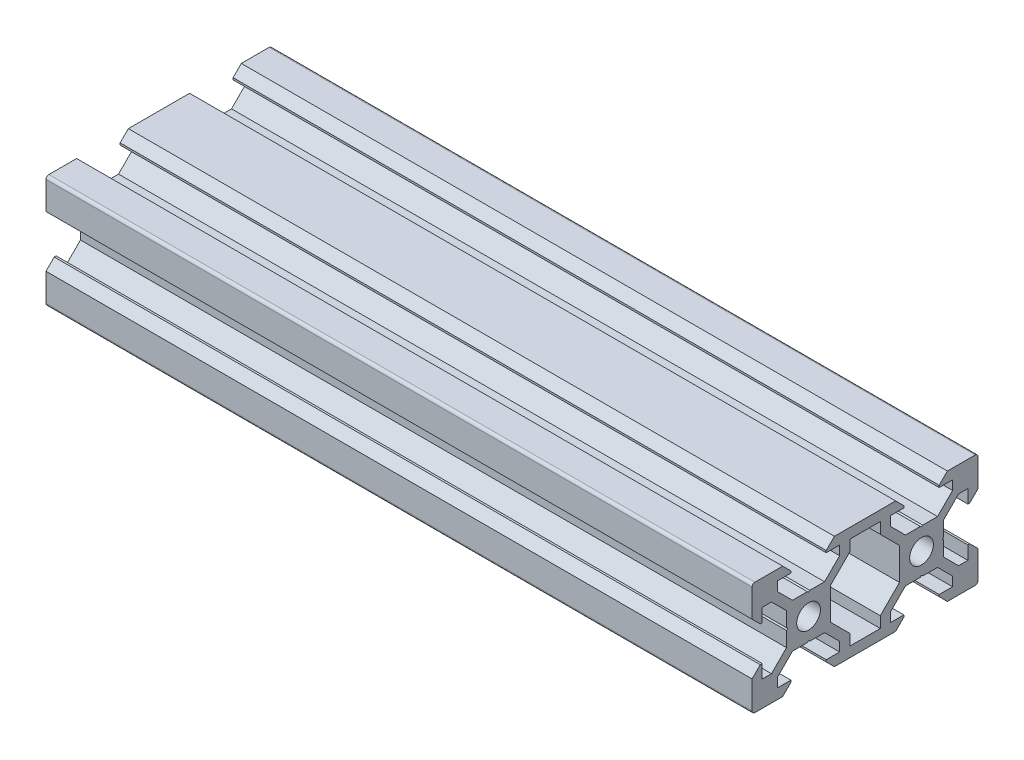
SolidWorks part; units mm, degrees
material "6061-T6 (SS)"
ref_plane "Top" through (0, 0, 0) normal (0, 0, 1) x (1, 0, 0)
ref_plane "Front" through (0, 0, 0) normal (0, 1, 0) x (1, 0, 0)
ref_plane "Right" through (0, 0, 0) normal (1, 0, 0) x (0, 0, -1)
sketch "Profile Sketch" plane through (0, 0, 0) normal (1, 0, 0) x (0, 0, -1)
  line L0 (5.42, 10) -> (-5.42, 10)
  line L1 (-4.5, 8.2) -> (-4.5, 6.56)
  line L2 (-4.5, 6.56) -> (-7.16, 3.9)
  line L3 (-7.16, 3.9) -> (-9.79, 3.9)
  line L4 (-9.79, 3.9) -> (-10, 3.69)
  line L5 (2.7, 8.2) -> (-2.7, 8.2)
  line L6 (-2.7, 8.2) -> (-2.7, 6.2387)
  line L7 (-2.7, 6.2387) -> (-6.1, 2.8387)
  line L8 (-6.1, 2.8387) -> (-6.1, -0.21)
  line L9 (-6.875, 8.545) -> (-6.875, 8.2)
  line L10 (-6.875, 8.2) -> (-4.5, 8.2)
  line L11 (-6.875, 8.545) -> (-5.42, 10)
  line L12 (0, -10) -> (0, 10) construction
  line L13 (-20, 0) -> (20, 0) construction
  line L14 (-10, -10) -> (-10, 10) construction
  line L15 (-6.875, -8.545) -> (-5.42, -10)
  line L16 (-6.875, -8.2) -> (-4.5, -8.2)
  line L17 (-6.875, -8.545) -> (-6.875, -8.2)
  line L18 (-2.7, -6.2387) -> (-6.1, -2.8387)
  line L19 (-2.7, -8.2) -> (-2.7, -6.2387)
  line L20 (2.7, -8.2) -> (-2.7, -8.2)
  line L21 (-7.16, -3.9) -> (-9.79, -3.9)
  line L22 (-4.5, -6.56) -> (-7.16, -3.9)
  line L23 (-4.5, -8.2) -> (-4.5, -6.56)
  line L24 (5.42, -10) -> (-5.42, -10)
  line L25 (-10, 0) -> (-20, 10) construction
  line L26 (-18.545, 3.125) -> (-18.2, 3.125)
  line L27 (-13.125, -8.545) -> (-13.125, -8.2)
  line L28 (-13.125, -8.2) -> (-15.5, -8.2)
  line L29 (-13.125, -8.545) -> (-14.58, -10)
  line L30 (-15.5, -8.2) -> (-15.5, -6.56)
  line L31 (-15.5, -6.56) -> (-12.84, -3.9)
  line L32 (-12.84, -3.9) -> (-10.21, -3.9)
  line L33 (-20, 4.58) -> (-20, 9.5)
  line L34 (-13.9, 2.8387) -> (-13.9, 0.21)
  line L35 (-16.56, 5.5) -> (-13.9, 2.8387)
  line L36 (-12.84, 3.9) -> (-10.21, 3.9)
  line L37 (-15.5, 6.56) -> (-12.84, 3.9)
  line L38 (-15.5, 8.2) -> (-15.5, 6.56)
  line L39 (-13.125, 8.545) -> (-14.58, 10)
  line L40 (-13.125, 8.2) -> (-15.5, 8.2)
  line L41 (-13.125, 8.545) -> (-13.125, 8.2)
  line L42 (-18.2, 3.125) -> (-18.2, 5.5)
  line L43 (-18.545, 3.125) -> (-20, 4.58)
  line L44 (-18.2, 5.5) -> (-16.56, 5.5)
  line L45 (-14.58, 10) -> (-19.5, 10)
  line L46 (-16.56, -5.5) -> (-13.9, -2.8387)
  line L47 (-14.58, -10) -> (-19.5, -10)
  line L48 (-18.2, -5.5) -> (-16.56, -5.5)
  line L49 (-18.545, -3.125) -> (-20, -4.58)
  line L50 (-18.2, -3.125) -> (-18.2, -5.5)
  line L51 (-20, -4.58) -> (-20, -9.5)
  line L52 (-18.545, -3.125) -> (-18.2, -3.125)
  line L53 (10, -10) -> (10, 10) construction
  line L54 (18.545, -3.125) -> (18.2, -3.125)
  line L55 (20, -4.58) -> (20, -9.5)
  line L56 (18.2, -3.125) -> (18.2, -5.5)
  line L57 (18.545, -3.125) -> (20, -4.58)
  line L58 (18.2, -5.5) -> (16.56, -5.5)
  line L59 (14.58, -10) -> (19.5, -10)
  line L60 (16.56, -5.5) -> (13.9, -2.8387)
  line L61 (14.58, 10) -> (19.5, 10)
  line L62 (18.2, 5.5) -> (16.56, 5.5)
  line L63 (18.545, 3.125) -> (20, 4.58)
  line L64 (18.2, 3.125) -> (18.2, 5.5)
  line L65 (13.125, 8.545) -> (13.125, 8.2)
  line L66 (13.125, 8.2) -> (15.5, 8.2)
  line L67 (13.125, 8.545) -> (14.58, 10)
  line L68 (15.5, 8.2) -> (15.5, 6.56)
  line L69 (15.5, 6.56) -> (12.84, 3.9)
  line L70 (12.84, 3.9) -> (10.21, 3.9)
  line L71 (16.56, 5.5) -> (13.9, 2.8387)
  line L72 (13.9, 2.8387) -> (13.9, 0.21)
  line L73 (20, 4.58) -> (20, 9.5)
  line L74 (12.84, -3.9) -> (10.21, -3.9)
  line L75 (15.5, -6.56) -> (12.84, -3.9)
  line L76 (15.5, -8.2) -> (15.5, -6.56)
  line L77 (13.125, -8.545) -> (14.58, -10)
  line L78 (13.125, -8.2) -> (15.5, -8.2)
  line L79 (13.125, -8.545) -> (13.125, -8.2)
  line L80 (18.545, 3.125) -> (18.2, 3.125)
  line L81 (4.5, -8.2) -> (4.5, -6.56)
  line L82 (4.5, -6.56) -> (7.16, -3.9)
  line L83 (7.16, -3.9) -> (9.79, -3.9)
  line L84 (2.7, -8.2) -> (2.7, -6.2387)
  line L85 (2.7, -6.2387) -> (6.1, -2.8387)
  line L86 (6.875, -8.545) -> (6.875, -8.2)
  line L87 (6.875, -8.2) -> (4.5, -8.2)
  line L88 (6.875, -8.545) -> (5.42, -10)
  line L89 (6.875, 8.545) -> (5.42, 10)
  line L90 (6.875, 8.2) -> (4.5, 8.2)
  line L91 (6.875, 8.545) -> (6.875, 8.2)
  line L92 (6.1, 2.8387) -> (6.1, -0.21)
  line L93 (2.7, 6.2387) -> (6.1, 2.8387)
  line L94 (2.7, 8.2) -> (2.7, 6.2387)
  line L95 (9.79, 3.9) -> (10, 3.69)
  line L96 (7.16, 3.9) -> (9.79, 3.9)
  line L97 (4.5, 6.56) -> (7.16, 3.9)
  line L98 (4.5, 8.2) -> (4.5, 6.56)
  line L99 (-10, 3.69) -> (-10.21, 3.9)
  line L100 (-10, -3.69) -> (-10.21, -3.9)
  line L101 (-9.79, -3.9) -> (-10, -3.69)
  line L102 (-13.9, -0.21) -> (-13.69, 0)
  line L103 (-13.69, 0) -> (-13.9, 0.21)
  line L104 (-13.9, -0.21) -> (-13.9, -2.8387)
  line L105 (-6.1, -0.21) -> (-6.31, 0)
  line L106 (-6.31, 0) -> (-6.1, -0.21)
  line L107 (-6.1, -0.21) -> (-6.1, -2.8387)
  line L108 (6.31, 0) -> (6.1, -0.21)
  line L109 (6.1, -0.21) -> (6.31, 0)
  line L110 (13.69, 0) -> (13.9, 0.21)
  line L111 (13.9, -0.21) -> (13.69, 0)
  line L112 (9.79, -3.9) -> (10, -3.69)
  line L113 (10, -3.69) -> (10.21, -3.9)
  line L114 (10, 3.69) -> (10.21, 3.9)
  line L115 (6.1, -0.21) -> (6.1, -2.8387)
  line L116 (13.9, -0.21) -> (13.9, -2.8387)
  line L118 (20, -10) -> (20, 10) construction
  line L119 (20, -10) -> (-20, -10) construction
  line L120 (-20, -10) -> (-20, 10) construction
  line L121 (20, 10) -> (-20, 10) construction
  line L122 (20, -10) -> (-20, 10) construction
  line L123 (-20, -10) -> (20, 10) construction
  circle A0 centre (-10, 0) radius 2.1
  arc A1 (-19.5, 10) -> (-20, 9.5) centre (-19.5, 9.5) ccw
  arc A2 (-19.5, -10) -> (-20, -9.5) centre (-19.5, -9.5) cw
  arc A3 (19.5, -10) -> (20, -9.5) centre (19.5, -9.5) ccw
  arc A4 (19.5, 10) -> (20, 9.5) centre (19.5, 9.5) cw
  circle A5 centre (10, 0) radius 2.1
  point P35 (-2.4957, 0)
  point P108 (0, -8.2)
  point P119 (0, 8.2)
  point P123 (2.4957, 0)
  point P131 (0, 0)
  point P143 (0, 0)
  dimension "D4" = 5.42
  dimension "D5" = 40
  dimension "D6" = 4.2
  dimension "D16" = 0.5
  dimension "D1" = 0.21
  dimension "D2" = 45
  dimension "D3" = 20
  dimension "D7" = 1.5
  dimension "D8" = 1.8
  dimension "D9" = 10
  dimension "D10" = 3.9
  dimension "D11" = 3.9
  dimension "D12" = 1.8
  dimension "D13" = 3.125
  dimension "D14" = 5.5
  dimension "D15" = 1.64
  dimension "D17" = 5.4
extrude "Profile Extrude" add sketch "Profile Sketch" along normal blind 125 contours A4 L61 L67 L65 L66 L68 L69 L70 L114 L95 L96 L97 L98 L90 L91 L89 L0 L11 L9 L10 L1 L2 L3 L4 L99 L36 L37 L38 L40 L41 L39 L45 A1 L33 L43 L26 L42 L44 L35 L34 L103 L102 L104 L46 L48 L50 L52 L49 L51 A2 L47 region at (0, 8.9563, -5.8313)
equation "\"M2x0.4_Tap_Hole_75\"= 1.6"
